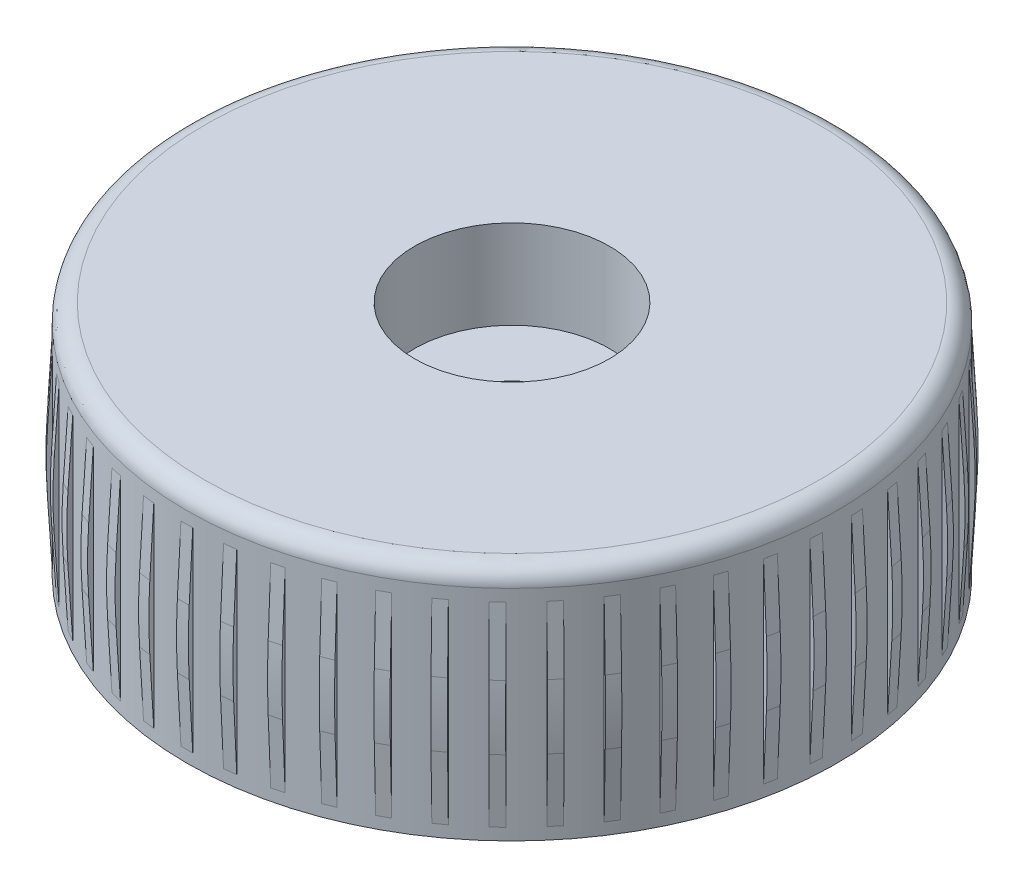
SolidWorks part; units mm, degrees
material "ABS"
ref_plane "Alzado" through (0, 0, 0) normal (0, 0, 1) x (1, 0, 0)
ref_plane "Planta" through (0, 0, 0) normal (0, 1, 0) x (1, 0, 0)
ref_plane "Vista lateral" through (0, 0, 0) normal (1, 0, 0) x (0, 0, -1)
sketch "Sketch1" plane through (0, 0, 0) normal (0, 1, 0) x (1, 0, 0)
  circle A0 centre (0, 0) radius 2.5
  circle A1 centre (0, 0) radius 27.5
  dimension "D1" = 5
  dimension "D2" = 55
extrude "Boss-Extrude1" add sketch "Sketch1" along normal blind 20
sketch "Sketch5" plane through (0, 20, 0) normal (0, 1, 0) x (1, 0, 0)
  circle A0 centre (0, 0) radius 22.225
extrude "Cut-Extrude3" cut sketch "Sketch5" against normal through all from offset 15 offset against normal yes
fillet "Fillet1" radius 1.5 1 edges at (0, 20, 27.5)
sketch "Sketch2" plane through (0, 0, 0) normal (1, 0, 0) x (0, 0, -1)
  line L0 (27.5, 17.5) -> (27.95, 9.25)
  line L1 (27.5, 0) -> (27.5, 18.5) construction
  line L2 (27.95, 9.25) -> (27.5, 1)
  line L3 (27.5, 17.5) -> (27.5, 1)
  line L4 (-27.5, 0) -> (27.5, 0) construction
  line L5 (-27.5, 18.5) -> (27.5, 18.5) construction
  point P9 (27.5, 9.25)
  dimension "D1" = 1
  dimension "D2" = 1
  dimension "D3" = 0.45
extrude "Boss-Extrude2" add sketch "Sketch2" along normal blind 0.5 and the other way blind 0.5 separate body
fillet "Fillet2" radius 50 1 edges at (0, 9.25, -27.95) type face fillet first side face at (0, 13.375, -27.725) second side face at (0, 5.125, -27.725)
pattern_circular "CirPattern3" count 50 over 360 about axis through (0, 18.5, 0) along (0, -1, 0) of bodies 102
sketch "Sketch6" plane through (0, 20, 0) normal (0, 1, 0) x (1, 0, 0)
  circle A0 centre (0, 0) radius 8.25
  dimension "D1" = 16.5
extrude "Cut-Extrude4" cut sketch "Sketch6" against normal blind 7.5
